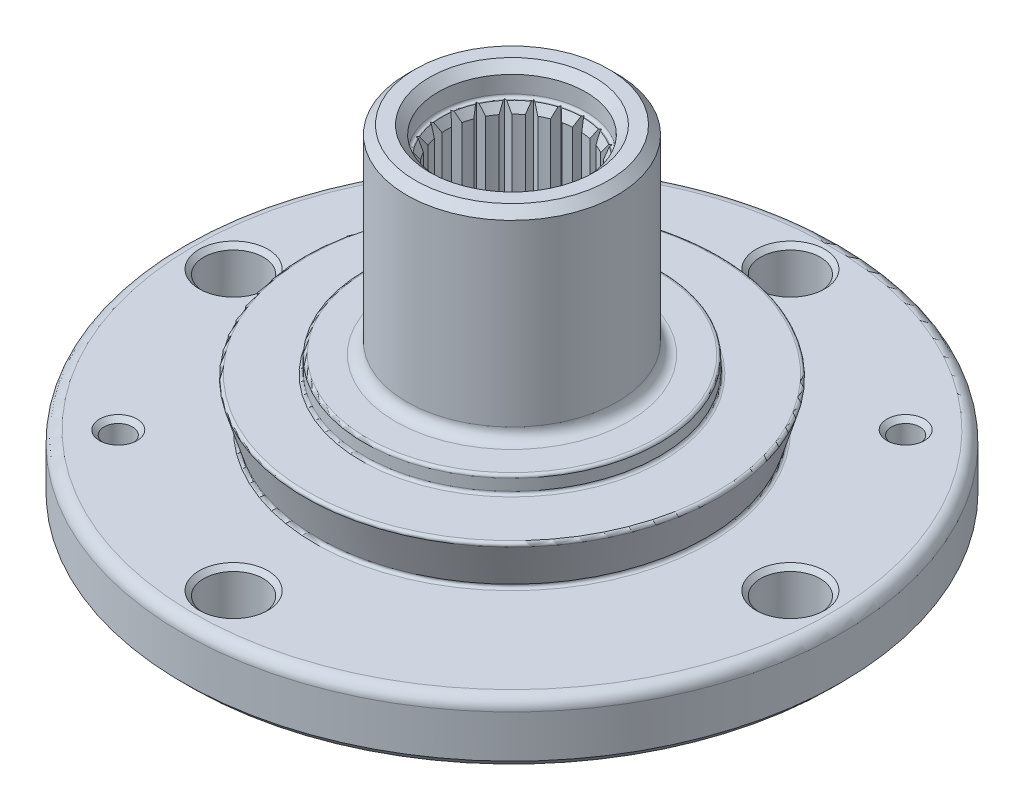
SolidWorks part; units mm, degrees
ref_plane "Plano frontal" through (0, 0, 0) normal (0, 0, 1) x (1, 0, 0)
ref_plane "Plano superior" through (0, 0, 0) normal (0, 1, 0) x (1, 0, 0)
ref_plane "Plano direito" through (0, 0, 0) normal (1, 0, 0) x (0, 0, -1)
sketch "Esboço1" plane through (0, 0, 0) normal (0, 0, 1) x (1, 0, 0)
  line L0 (9.166, -37.5494) -> (9.166, 45.4392) construction
  line L1 (22.166, 33) -> (20.666, 33)
  line L2 (22.166, 33) -> (22.166, 38)
  line L3 (22.166, 38) -> (27.666, 38)
  line L4 (27.666, 38) -> (27.666, 3)
  line L5 (27.666, 3) -> (35.166, 3)
  line L6 (35.166, 3) -> (35.166, 0)
  line L7 (35.166, 0) -> (45.766, 0)
  line L8 (45.766, 0) -> (43.166, -8.5)
  line L9 (43.166, -8.5) -> (67.166, -8.5)
  line L10 (67.166, -8.5) -> (67.166, -19.5)
  line L11 (67.166, -19.5) -> (38.666, -19.5)
  line L12 (38.666, -19.5) -> (38.666, -25.5)
  line L13 (38.666, -25.5) -> (38.166, -25.5)
  line L14 (38.166, -25.5) -> (38.166, -39.5)
  line L15 (38.166, -39.5) -> (34.166, -39.5)
  line L16 (32.166, -27.5) -> (33.166, -27.5)
  line L17 (33.166, -27.5) -> (34.166, -39.5)
  line L18 (32.166, -27.5) -> (32.166, -20.5)
  line L19 (32.166, -20.5) -> (20.666, -20.5)
  line L20 (20.666, -20.5) -> (20.666, 33)
  dimension "D1" = 11.5
  dimension "D2" = 13
  dimension "D3" = 18.5
  dimension "D4" = 26
  dimension "D5" = 36.6
  dimension "D6" = 34
  dimension "D7" = 58
  dimension "D8" = 29.5
  dimension "D9" = 29
  dimension "D10" = 25
  dimension "D11" = 24
  dimension "D12" = 23
  dimension "D13" = 5
  dimension "D14" = 35
  dimension "D15" = 38
  dimension "D16" = 46.5
  dimension "D17" = 6
  dimension "D18" = 11
  dimension "D19" = 20
  dimension "D20" = 7
  dimension "D21" = 19
revolve "Revolução1" add sketch "Esboço1" angle 360 about L0
sketch "Esboço2" plane through (0, -20.5, 0) normal (0, -1, 0) x (1, 0, 0)
  line L0 (7.916, 10.7535) -> (10.416, 10.7535)
  line L1 (9.166, 0) -> (9.166, 15.8018) construction
  line L2 (9.166, 12.7255) -> (7.916, 10.7535)
  line L3 (10.416, 10.7535) -> (9.166, 12.7255)
  line L4 (10.9962, 10.6701) -> (13.395, 9.9658)
  line L5 (12.7512, 12.21) -> (10.9962, 10.6701)
  line L6 (13.395, 9.9658) -> (12.7512, 12.21)
  line L7 (13.9282, 9.7223) -> (16.0313, 8.3706)
  line L8 (16.0459, 10.7054) -> (13.9282, 9.7223)
  line L9 (16.0313, 8.3706) -> (16.0459, 10.7054)
  line L10 (16.4744, 7.9868) -> (18.1115, 6.0974)
  line L11 (18.7833, 8.3334) -> (16.4744, 7.9868)
  line L12 (18.1115, 6.0974) -> (18.7833, 8.3334)
  line L13 (18.4285, 5.6042) -> (19.467, 3.3301)
  line L14 (20.7415, 5.2864) -> (18.4285, 5.6042)
  line L15 (19.467, 3.3301) -> (20.7415, 5.2864)
  line L16 (19.6322, 2.7677) -> (19.988, 0.2931)
  line L17 (21.7619, 1.811) -> (19.6322, 2.7677)
  line L18 (19.988, 0.2931) -> (21.7619, 1.811)
  line L19 (19.988, -0.2931) -> (19.6322, -2.7677)
  line L20 (21.7619, -1.811) -> (19.988, -0.2931)
  line L21 (19.6322, -2.7677) -> (21.7619, -1.811)
  line L22 (19.467, -3.3301) -> (18.4285, -5.6042)
  line L23 (20.7415, -5.2864) -> (19.467, -3.3301)
  line L24 (18.4285, -5.6042) -> (20.7415, -5.2864)
  line L25 (18.1115, -6.0974) -> (16.4744, -7.9868)
  line L26 (18.7833, -8.3334) -> (18.1115, -6.0974)
  line L27 (16.4744, -7.9868) -> (18.7833, -8.3334)
  line L28 (16.0313, -8.3706) -> (13.9282, -9.7223)
  line L29 (16.0459, -10.7054) -> (16.0313, -8.3706)
  line L30 (13.9282, -9.7223) -> (16.0459, -10.7054)
  line L31 (13.395, -9.9658) -> (10.9962, -10.6701)
  line L32 (12.7512, -12.21) -> (13.395, -9.9658)
  line L33 (10.9962, -10.6701) -> (12.7512, -12.21)
  line L34 (10.416, -10.7535) -> (7.916, -10.7535)
  line L35 (9.166, -12.7255) -> (10.416, -10.7535)
  line L36 (7.916, -10.7535) -> (9.166, -12.7255)
  line L37 (7.3357, -10.6701) -> (4.937, -9.9658)
  line L38 (5.5808, -12.21) -> (7.3357, -10.6701)
  line L39 (4.937, -9.9658) -> (5.5808, -12.21)
  line L40 (4.4037, -9.7223) -> (2.3006, -8.3706)
  line L41 (2.2861, -10.7054) -> (4.4037, -9.7223)
  line L42 (2.3006, -8.3706) -> (2.2861, -10.7054)
  line L43 (1.8576, -7.9868) -> (0.2204, -6.0974)
  line L44 (-0.4513, -8.3334) -> (1.8576, -7.9868)
  line L45 (0.2204, -6.0974) -> (-0.4513, -8.3334)
  line L46 (-0.0965, -5.6042) -> (-1.135, -3.3301)
  line L47 (-2.4095, -5.2864) -> (-0.0965, -5.6042)
  line L48 (-1.135, -3.3301) -> (-2.4095, -5.2864)
  line L49 (-1.3002, -2.7677) -> (-1.656, -0.2931)
  line L50 (-3.43, -1.811) -> (-1.3002, -2.7677)
  line L51 (-1.656, -0.2931) -> (-3.43, -1.811)
  line L52 (-1.656, 0.2931) -> (-1.3002, 2.7677)
  line L53 (-3.43, 1.811) -> (-1.656, 0.2931)
  line L54 (-1.3002, 2.7677) -> (-3.43, 1.811)
  line L55 (-1.135, 3.3301) -> (-0.0965, 5.6042)
  line L56 (-2.4095, 5.2864) -> (-1.135, 3.3301)
  line L57 (-0.0965, 5.6042) -> (-2.4095, 5.2864)
  line L58 (0.2204, 6.0974) -> (1.8576, 7.9868)
  line L59 (-0.4513, 8.3334) -> (0.2204, 6.0974)
  line L60 (1.8576, 7.9868) -> (-0.4513, 8.3334)
  line L61 (2.3006, 8.3706) -> (4.4037, 9.7223)
  line L62 (2.2861, 10.7054) -> (2.3006, 8.3706)
  line L63 (4.4037, 9.7223) -> (2.2861, 10.7054)
  line L64 (4.937, 9.9658) -> (7.3357, 10.6701)
  line L65 (5.5808, 12.21) -> (4.937, 9.9658)
  line L66 (7.3357, 10.6701) -> (5.5808, 12.21)
  dimension "D1" = 1.25
  dimension "D2" = 1.25
  dimension "D3" = 22
extrude "Corte-extrusão3" cut sketch "Esboço2" against normal through all
chamfer "Chanfro3" distance 1.5 angle 30 22 edges at (-1.8682, 33, -3.2399) (-2.334, 33, 0) (-1.8682, 33, 3.2399) (-0.5084, 33, 6.2174) (1.6351, 33, 8.6911) (4.3887, 33, 10.4608) (7.5294, 33, 11.3829) (10.8026, 33, 11.3829) (13.9433, 33, 10.4608) (16.6969, 33, 8.6911) (20.2001, 33, 3.2399) (18.8404, 33, 6.2174) (20.666, 33, 0) (20.2001, 33, -3.2399) (18.8404, 33, -6.2174) (16.6969, 33, -8.6911) (13.9433, 33, -10.4608) (10.8026, 33, -11.3829) (7.5294, 33, -11.3829) (4.3887, 33, -10.4608) (1.6351, 33, -8.6911) (-0.5084, 33, -6.2174) first distance on face at (-1.8532, 6.25, -3.2355) first distance on face at (-2.3184, 6.25, 0) first distance on face at (-1.8532, 6.25, 3.2355) first distance on face at (-0.4953, 6.25, 6.2089) first distance on face at (1.6453, 6.25, 8.6793) first distance on face at (4.3952, 6.25, 10.4466) first distance on face at (7.5316, 6.25, 11.3675) first distance on face at (10.8004, 6.25, 11.3675) first distance on face at (13.9368, 6.25, 10.4466) first distance on face at (16.6867, 6.25, 8.6793) first distance on face at (20.1852, 6.25, 3.2355) first distance on face at (18.8273, 6.25, 6.2089) first distance on face at (20.6504, 6.25, 0) first distance on face at (20.1852, 6.25, -3.2355) first distance on face at (18.8273, 6.25, -6.2089) first distance on face at (16.6867, 6.25, -8.6793) first distance on face at (13.9368, 6.25, -10.4466) first distance on face at (10.8004, 6.25, -11.3675) first distance on face at (7.5316, 6.25, -11.3675) first distance on face at (4.3952, 6.25, -10.4466) first distance on face at (1.6453, 6.25, -8.6793) first distance on face at (-0.4953, 6.25, -6.2089)
fillet "Filete3" radius 0.5 1 edges at (22.166, 33, 0)
chamfer "Chanfro4" distance 1.5 angle 45 2 edges at (27.666, 38, 0) (22.166, 38, 0)
fillet "Filete5" radius 2 1 edges at (27.666, 3, 0)
fillet "Filete6" radius 0.5 4 edges at (43.166, -8.5, 0) (45.766, 0, 0) (35.166, 0, 0) (35.166, 3, 0)
fillet "Filete7" radius 2 1 edges at (67.166, -8.5, 0)
fillet "Filete8" radius 1 1 edges at (38.666, -19.5, 0)
fillet "Filete9" radius 0.5 1 edges at (38.166, -25.5, 0)
chamfer "Chanfro5" distance 1 angle 45 2 edges at (38.166, -39.5, 0) (34.166, -39.5, 0) first distance on face at (38.166, -26, 0) first distance on face at (38.166, -39.5, 0)
chamfer "Chanfro6" distance 1.5 angle 45 1 edges at (67.166, -19.5, 0)
fillet "Filete10" radius 2 1 edges at (33.166, -27.5, 0)
fillet "Filete11" radius 1 1 edges at (32.166, -20.5, 0)
chamfer "Chanfro7" distance 1 angle 30 22 edges at (-2.334, -20.5, 0) (-1.8682, -20.5, -3.2399) (-0.5084, -20.5, -6.2174) (1.6351, -20.5, -8.6911) (4.3887, -20.5, -10.4608) (7.5294, -20.5, -11.3829) (10.8026, -20.5, -11.3829) (13.9433, -20.5, -10.4608) (16.6969, -20.5, -8.6911) (18.8404, -20.5, -6.2174) (20.2001, -20.5, -3.2399) (20.666, -20.5, 0) (20.2001, -20.5, 3.2399) (18.8404, -20.5, 6.2174) (16.6969, -20.5, 8.6911) (13.9433, -20.5, 10.4608) (10.8026, -20.5, 11.3829) (7.5294, -20.5, 11.3829) (4.3887, -20.5, 10.4608) (1.6351, -20.5, 8.6911) (-0.5084, -20.5, 6.2174) (-1.8682, -20.5, 3.2399) first distance on face at (31.166, -20.5, 0)
sketch "Esboço3" plane through (0, -19.5, 0) normal (0, -1, 0) x (1, 0, 0)
  line L0 (9.166, 0) -> (9.166, 61.2798) construction
  circle A0 centre (9.166, 0) radius 49 construction
  circle A1 centre (-39.834, 0) radius 5.25
  circle A3 centre (9.166, 49) radius 5.25
  circle A4 centre (-25.4823, 34.6482) radius 2.5
  circle A5 centre (58.166, 0) radius 5.25
  circle A7 centre (9.166, -49) radius 5.25
  circle A8 centre (43.8142, -34.6482) radius 2.5
  circle A10 centre (-25.4823, -34.6482) radius 5.25 [skipped]
  circle A11 centre (43.8142, 34.6482) radius 5.25 [skipped]
  circle A12 centre (-25.4823, 34.6482) radius 5.25 [skipped]
  circle A13 centre (43.8142, -34.6482) radius 5.25 [skipped]
  dimension "D1" = 98
  dimension "D2" = 10.5
  dimension "D4" = 5
  dimension "D5" = 5
  dimension "D3" = 8
extrude "Corte-extrusão4" cut sketch "Esboço3" against normal through all
chamfer "Chanfro8" distance 0.8 angle 45 11 edges at (14.416, -19.5, -49) (3.916, -8.5, -49) (52.916, -8.5, 0) (63.416, -19.5, 0) (41.3142, -8.5, -34.6482) (-45.084, -8.5, 0) (-34.584, -19.5, 0) (-22.9823, -19.5, 34.6482) (-27.9823, -8.5, 34.6482) (3.916, -8.5, 49) (14.416, -19.5, 49)
